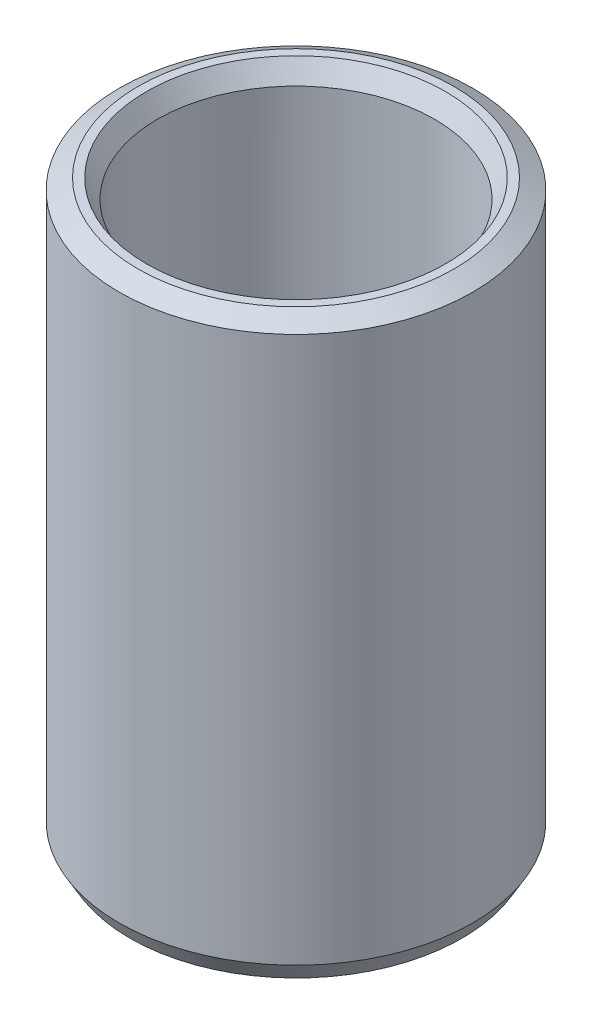
SolidWorks part; units mm, degrees
ref_plane "Front Plane" through (0, 0, 0) normal (0, 0, 1) x (1, 0, 0)
ref_plane "Top Plane" through (0, 0, 0) normal (0, 1, 0) x (1, 0, 0)
ref_plane "Right Plane" through (0, 0, 0) normal (1, 0, 0) x (0, 0, -1)
sketch "Sketch1" plane through (0, 0, 0) normal (0, 1, 0) x (1, 0, 0)
  circle A0 centre (0, 0) radius 45
  dimension "SLEEVE_OD" = 90
extrude "Boss-Extrude1" add sketch "Sketch1" along normal blind 146.6112
sketch "Sketch2" plane through (0, 0, 0) normal (0, 1, 0) x (1, 0, 0)
  circle A0 centre (0, 0) radius 35.3049
  dimension "BORE_D" = 70.6099
extrude "Cut-Extrude1" cut sketch "Sketch2" along normal through all
chamfer "Chamfer1" distance 2.7446 angle 60 4 edges at (0, 146.6112, 35.3049) (0, 0, 35.3049) (0, 0, 45) (0, 146.6112, 45) first distance on face at (0, 146.6112, 35.3049) first distance on face at (0, 0, 35.3049) first distance on face at (0, 146.6112, 45)
